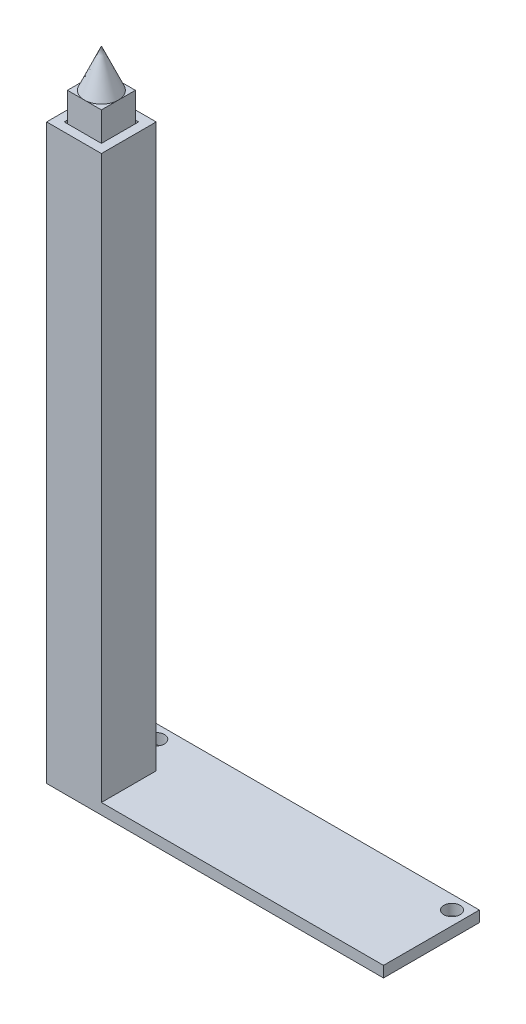
SolidWorks part; units mm, degrees
ref_plane "Front Plane" through (0, 0, 0) normal (0, 0, 1) x (1, 0, 0)
ref_plane "Top Plane" through (0, 0, 0) normal (0, 1, 0) x (1, 0, 0)
ref_plane "Right Plane" through (0, 0, 0) normal (1, 0, 0) x (0, 0, -1)
sketch "Sketch1" plane through (0, 0, 0) normal (0, 1, 0) x (1, 0, 0)
  line L0 (-30.75, -3.75) -> (-30.75, 6.25) construction
  line L1 (30.75, -8.75) -> (-30.75, -8.75)
  line L2 (30.75, -8.75) -> (30.75, 8.75)
  line L3 (30.75, 8.75) -> (-30.75, 8.75)
  line L4 (-30.75, -8.75) -> (-30.75, 8.75)
  line L5 (30.75, -8.75) -> (-30.75, 8.75) construction
  line L6 (30.75, 8.75) -> (-30.75, -8.75) construction
  line L7 (-20.75, -8.75) -> (-30.75, -8.75)
  line L8 (-20.75, -8.75) -> (-20.75, 1.25)
  line L9 (-20.75, 1.25) -> (-30.75, 1.25)
  line L10 (-30.75, -8.75) -> (-30.75, 1.25)
  line L11 (-21.75, -7.75) -> (-21.75, 0.25)
  line L12 (-21.75, 0.25) -> (-29.75, 0.25)
  line L13 (-29.75, -7.75) -> (-29.75, 0.25)
  line L14 (-21.75, -7.75) -> (-29.75, -7.75)
  circle A0 centre (-25.75, 6.25) radius 1.5
  circle A1 centre (28.25, 6.25) radius 1.5
  point P0 (0, 0)
  point P14 (-25.75, 1.25)
  point P15 (0, 0)
  dimension "D1" = 3
  dimension "D2" = 3
  dimension "D3" = 10
  dimension "D4" = 54
  dimension "D5" = 10
  dimension "D7" = 2.5
  dimension "D8" = 2.5
  dimension "D6" = 1
extrude "Boss-Extrude5" add sketch "Sketch1" along normal blind 2 contours L9 L8 L1 L2 L3 L4 A1 A0 | L14 L11 L12 L13 | L8 L9 L10 L7 region at (2.658, 0, -0.2979) region at (-25.75, 0, 3.75)
extrude "Boss-Extrude6" add sketch "Sketch1<5>" along normal blind 101.6 contours L8 L9 L4 L1 L11 L14 L13 L12 region at (-25.75, 0, 8.6086)
sketch "Sketch1<5>" plane through (0, 0, 0) normal (0, 1, 0) x (1, 0, 0) same geometry as "Sketch1"
sketch "Sketch8" plane through (0, 101.6, 0) normal (0, 1, 0) x (1, 0, 0)
  line L10 (-20.75, -8.75) -> (-30.75, -8.75) construction
  line L11 (-20.75, -8.75) -> (-20.75, 1.25) construction
  line L12 (-30.75, 1.25) -> (-20.75, 1.25) construction
  line L13 (-30.75, -8.75) -> (-30.75, 1.25) construction
  line L14 (-29.15, -7.15) -> (-22.35, -7.15)
  line L15 (-22.35, -7.15) -> (-22.35, -0.35)
  line L16 (-22.35, -0.35) -> (-29.15, -0.35)
  line L17 (-29.15, -0.35) -> (-29.15, -7.15)
  line L18 (-29.15, -7.15) -> (-22.35, -7.15)
  line L19 (-22.35, -7.15) -> (-22.35, -0.35)
  line L20 (-22.35, -0.35) -> (-29.15, -0.35)
  line L21 (-29.15, -0.35) -> (-29.15, -7.15)
  line L22 (-20.75, -8.75) -> (-30.75, -8.75)
  line L23 (-20.75, -8.75) -> (-20.75, 1.25)
  line L24 (-30.75, 1.25) -> (-20.75, 1.25)
  line L25 (-30.75, -8.75) -> (-30.75, 1.25)
  line M5 (-20.75, -8.75) -> (-20.75, 1.25)
  line M6 (-20.75, 1.25) -> (-30.75, 1.25)
  line M7 (-30.75, 1.25) -> (-30.75, -8.75)
  line M8 (-30.75, -8.75) -> (-20.75, -8.75)
  line M9 (-21.75, 0.25) -> (-21.75, -7.75)
  line M10 (-21.75, -7.75) -> (-29.75, -7.75)
  line M11 (-29.75, -7.75) -> (-29.75, 0.25)
  line M12 (-29.75, 0.25) -> (-21.75, 0.25)
  dimension "D1" = 0.6
extrude "Boss-Extrude11" add sketch "Sketch8" along normal blind 3 contours M8 M5 M6 M7 M12 M9 M10 M11 | L21 L20 L19 L18 M9 M12 M11 M10 region at (-25.75, 101.6, 8.6086) region at (-21.8631, 101.6, 3.75)
sketch "Sketch9" plane through (0, 0, 0) normal (0, -1, 0) x (1, 0, 0)
  line L14 (-29.45, 0.05) -> (-22.05, 0.05)
  line L15 (-22.05, 0.05) -> (-22.05, 7.45)
  line L16 (-29.45, 7.45) -> (-29.45, 0.05)
  line L17 (-22.05, 7.45) -> (-29.45, 7.45)
  line L18 (-29.45, 0.05) -> (-22.05, 0.05)
  line L19 (-22.05, 0.05) -> (-22.05, 7.45)
  line L20 (-29.45, 7.45) -> (-29.45, 0.05)
  line L21 (-22.05, 7.45) -> (-29.45, 7.45)
  dimension "D1" = 0.3
extrude "Boss-Extrude12" add sketch "Sketch9" against normal blind 3 separate body
sketch "Sketch10" plane through (0, 3, 0) normal (0, 1, 0) x (1, 0, 0)
  line L13 (-28.85, -6.85) -> (-22.65, -6.85)
  line L14 (-22.65, -6.85) -> (-22.65, -0.65)
  line L15 (-28.85, -0.65) -> (-28.85, -6.85)
  line L16 (-22.65, -0.65) -> (-28.85, -0.65)
  line L17 (-28.85, -6.85) -> (-22.65, -6.85)
  line L18 (-22.65, -6.85) -> (-22.65, -0.65)
  line L19 (-28.85, -0.65) -> (-28.85, -6.85)
  line L20 (-22.65, -0.65) -> (-28.85, -0.65)
  dimension "D1" = 0.3
extrude "Boss-Extrude13" add sketch "Sketch10" along normal offset from surface (106.6 mm away) 5 up to face at (-25.75, 104.6, 3.75) offset beyond the face yes
ref_plane "Plane3" through (0, 0, 3.75) normal (0, 0, -1) x (-1, 0, 0)
sketch "Sketch11" plane through (0, 0, 3.75) normal (0, 0, -1) x (-1, 0, 0)
  line L0 (28.85, 109.6) -> (25.75, 116.6)
  line L1 (25.75, 116.6) -> (25.75, 109.6)
  line L2 (22.65, 109.6) -> (28.85, 109.6) construction
  line L3 (25.75, 109.6) -> (28.85, 109.6)
  dimension "D1" = 7
revolve "Revolve2" add sketch "Sketch11" angle 360 about L1
